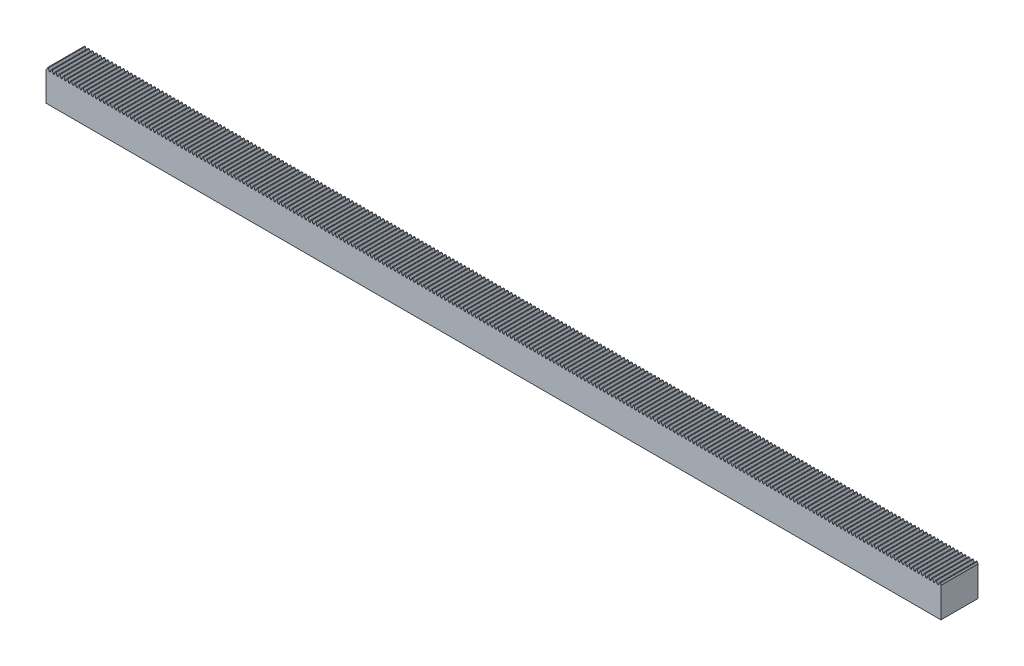
SolidWorks part; units mm, degrees
extrude "Blank" add sketch "BlankSke" against normal blind 60
sketch "BlankSke" plane through (0, 0, 0) normal (0, 0, 1) x (1, 0, 0)
  line L1 (0, 0) -> (1450, 0)
  line L2 (0, 0) -> (0, 51.4)
  line L3 (0, 51.4) -> (1450, 51.4)
  line L4 (1450, 0) -> (1450, 51.4)
  dimension "Length" = 1450
ref_plane "Plane1" through (0, 0, 0) normal (0, 0, 1) x (1, 0, 0)
ref_plane "Plane2" through (0, 0, 0) normal (0, 1, 0) x (1, 0, 0)
ref_plane "Plane3" through (0, 0, 0) normal (1, 0, 0) x (0, 0, -1)
sketch "HoldingSke" plane through (0, 0, 0) normal (0, 1, 0) x (1, 0, 0)
  line L0 (0, 0) -> (0.0696, 0.4951)
  line L1 (-15, 0) -> (100, 0) construction
  line L2 (0, 0) -> (-2.1039, 2.3779)
  line L3 (0, 0) -> (-11.863, 4.5341)
  line L4 (0, 0) -> (-5.3169, -6.8053)
  line L5 (0, 0) -> (-23.7986, -8.8762)
  line L6 (0, 0) -> (-10.5278, -7.1032)
  line L9 (-71.009, 38.7566) -> (1291.5453, 534.6858)
  line L10 (-76.2, 4.3779) -> (-26.8, 4.3779)
  line L11 (0, 0) -> (-60, 0)
  line L12 (-76.2, 101.6) -> (-76.133, 101.6)
  line L13 (24.9733, 27.94) -> (52.9518, 28.4284)
  line L14 (24.9733, 27.94) -> (24.9743, 27.94)
  line L15 (24.9733, 27.94) -> (100.4006, 29.5858)
  circle A0 centre (0, 0) radius 19.05
  circle A1 centre (0, 0) radius 24.7
  circle A2 centre (0, 0) radius 12.7
  dimension "Num_teeth" = 232
  dimension "Width" = 60
  dimension "Length" = 1450
  dimension "Pitch_height" = 49.4
sketch "TooCutSkeIll" plane through (0, 0, 0) normal (0, 0, 1) x (1, 0, 0)
  line L0 (-2.4806, 51.3474) -> (-0.9819, 47.2296)
  line L1 (-0.5111, 46.9) -> (0.5111, 46.9)
  line L2 (0.9819, 47.2296) -> (2.4806, 51.3474)
  line L3 (1450, 51.4) -> (0, 51.4) construction
  line L4 (0, 0) -> (0, 64.897) construction
  line L5 (-13.208, 49.4) -> (12.954, 49.4) construction
  line L6 (0, 0) -> (1450, 0) construction
  line L7 (1.7718, 49.4) -> (1.7718, 48.7463) construction
  line L8 (-1.7718, 49.4) -> (-1.7718, 48.7463) construction
  line L9 (2.5558, 51.4) -> (2.5558, 51.4254)
  line L10 (-2.5558, 51.4) -> (-2.5558, 51.4254)
  line L11 (-2.5558, 51.4254) -> (2.5558, 51.4254)
  arc A0 (0.5111, 46.9) -> (0.9819, 47.2296) centre (0.5111, 47.401) ccw
  arc A1 (-0.9819, 47.2296) -> (-0.5111, 46.9) centre (-0.5111, 47.401) ccw
  arc A2 (2.5558, 51.4) -> (2.4806, 51.3474) centre (2.5558, 51.32) ccw
  arc A3 (-2.4806, 51.3474) -> (-2.5558, 51.4) centre (-2.5558, 51.32) ccw
  dimension "Addendum_plus" = 2.0254
  dimension "Pitch_height" = 49.4
  dimension "Pressure_angle" = 20
  dimension "Gap_width" = 3.5436
  dimension "Dedendum" = 2.5
extrude "ToothCutIll" [suppressed] cut sketch "TooCutSkeIll" against normal through all
sketch "TooCutSkeSim" plane through (0, 0, 0) normal (0, 0, 1) x (1, 0, 0)
  line L0 (0.8619, 46.9) -> (-0.8619, 46.9)
  line L1 (2.509, 51.4254) -> (0.8619, 46.9)
  line L2 (0, 17.4625) -> (0, 53.467) construction
  line L3 (2.509, 51.4254) -> (-2.509, 51.4254)
  line L6 (-2.509, 51.4254) -> (-0.8619, 46.9)
  line L9 (-1.7718, 49.4) -> (1.7718, 49.4) construction
  line L10 (0, 0) -> (1450, 0) construction
  line L11 (1.7718, 49.4) -> (1.7718, 53.467) construction
  line L12 (-1.7718, 49.4) -> (-1.7718, 53.467) construction
  dimension "Addendum_plus" = 2.0254
  dimension "Pitch_height" = 49.4
  dimension "Pressure_angle" = 20
  dimension "Gap_width" = 3.5436
  dimension "Dedendum" = 2.5
extrude "ToothCutSim" cut sketch "TooCutSkeSim" against normal through all
pattern_linear "TeethCuts" count 232 spacing 6.2832 along (1, 0, 0) of "ToothCutIll", "ToothCutSim"
equation "' \"Module@HoldingSke\" = 6.35"
equation "' \"Num_teeth@HoldingSke\" = 12"
equation "' \"Ap@HoldingSke\" =  20"
equation "' \"Ap@HoldingSke\" = 20"
equation "' \"Width@HoldingSke\" = 0.25 * 25.4"
equation "' \"Show_teeth@HoldingSke\" = 500"
equation "' \"Backlash@HoldingSke\" = 0.009 * 25.4"
equation "' \"Addendum_fac@HoldingSke\" = 1.0"
equation "' \"Dedendum_fac@HoldingSke\" = 1.25"
equation "' \"Dedendum_add@HoldingSke\" = 0.00005 * 25.4"
equation "' \"Clearance_fac@HoldingSke\" = 0.25"
equation "' \"Pitch_height@HoldingSke\" = 1 * 25.4"
equation "' \"Length@HoldingSke\" = 4.71 * 25.4"
equation "\"Pitch@HoldingSke\" = 1 / \"Module@HoldingSke\""
equation "\"MPH@HoldingSke\" = \"Dedendum_fac@HoldingSke\" / \"Pitch@HoldingSke\" + 2 * \"Dedendum_add@HoldingSke\" + 0.002 * 25.4"
equation "\"MPH@HoldingSke\" = ((sgn( \"MPH@HoldingSke\" - \"Pitch_height@HoldingSke\")+1)*( \"MPH@HoldingSke\" - \"Pitch_height@HoldingSke\"))/2 + \"Pitch_height@HoldingSke\""
equation "\"Blank_height@BlankSke\" = \"Pitch_height@HoldingSke\" + \"Addendum_fac@HoldingSke\"  / \"Pitch@HoldingSke\" "
equation "\"Length@BlankSke\" =  \"Length@HoldingSke\""
equation "\"Face_width@Blank\" = \"Width@HoldingSke\""
equation "\"Pressure_angle@TooCutSkeIll\" = \"Ap@HoldingSke\""
equation "\"Addendum_plus@TooCutSkeIll\" =  \"Addendum_fac@HoldingSke\"  / \"Pitch@HoldingSke\" + 0.001 *25.4"
equation "\"Dedendum@TooCutSkeIll\" = \"Dedendum_fac@HoldingSke\"  / \"Pitch@HoldingSke\""
equation "\"Pitch_height@TooCutSkeIll\" =  \"MPH@HoldingSke\""
equation "\"Gap_width@TooCutSkeIll\" = 3.14159265 / 2 / \"Pitch@HoldingSke\" + 6 * \"Backlash@HoldingSke\""
equation "\"Pressure_angle@TooCutSkeSim\" = \"Ap@HoldingSke\""
equation "\"Addendum_plus@TooCutSkeSim\" =  \"Addendum_fac@HoldingSke\"  / \"Pitch@HoldingSke\" + 0.001 * 25.4"
equation "\"Dedendum@TooCutSkeSim\" = \"Dedendum_fac@HoldingSke\"  / \"Pitch@HoldingSke\""
equation "\"Pitch_height@TooCutSkeSim\" =  \"MPH@HoldingSke\""
equation "\"Gap_width@TooCutSkeSim\" = 3.14159265 / 2 / \"Pitch@HoldingSke\" + 6 * \"Backlash@HoldingSke\""
equation "\"Root_fillet@TooCutSkeIll\" = \"Clearance_fac@HoldingSke\" / \"Pitch@HoldingSke\" + \"Dedendum_add@HoldingSke\""
equation "\"Break_rad@TooCutSkeIll\" = 0.02 / \"Pitch@HoldingSke\" * 2"
equation "\"Linear_pitch@TeethCuts\" = 3.14159265 / \"Pitch@HoldingSke\""
equation "\"Num_teeth@HoldingSke\" = int( ( \"Length@HoldingSke\" + 0 ) / (3.14159265 / \"Pitch@HoldingSke\")) + 0.9999  + 1"
equation " \"Num_teeth@TeethCuts\" = int( \"Show_teeth@HoldingSke\" ) + 1"
equation " \"Num_teeth@TeethCuts\" = ((sgn( \"Num_teeth@TeethCuts\" - \"Num_teeth@HoldingSke\" )-1)*( \"Num_teeth@TeethCuts\" - \"Num_teeth@HoldingSke\" ))/-2+ \"Num_teeth@HoldingSke\""
equation " \"Num_teeth@TeethCuts\" = ((sgn( \"Num_teeth@TeethCuts\" - 2.0)+1)*( \"Num_teeth@TeethCuts\" - 2.0))/2 +2.0"
